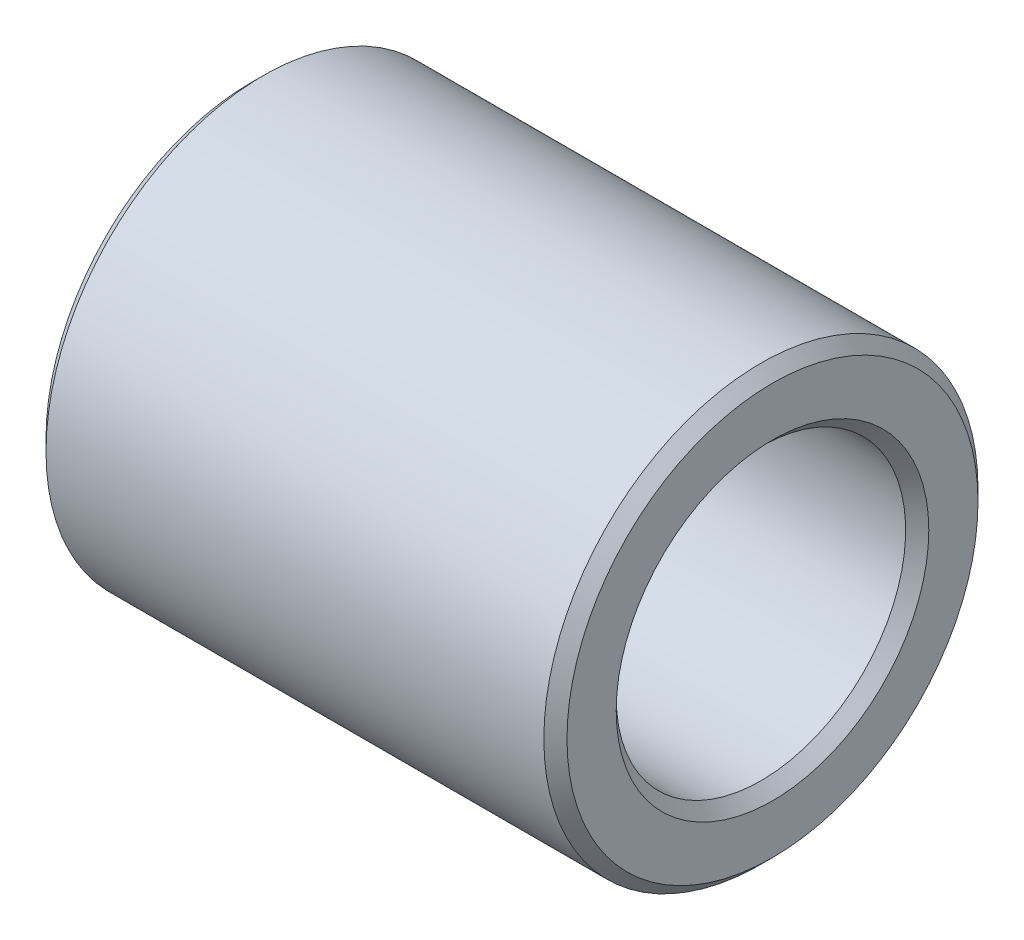
SolidWorks part; units mm, degrees
material "6061-T6 (SS)"
ref_plane "Front Plane" through (0, 0, 0) normal (0, 0, 1) x (1, 0, 0)
ref_plane "Top Plane" through (0, 0, 0) normal (0, 1, 0) x (1, 0, 0)
ref_plane "Right Plane" through (0, 0, 0) normal (1, 0, 0) x (0, 0, -1)
sketch "Sketch1" plane through (0, 0, 0) normal (0, 0, 1) x (1, 0, 0)
  line L0 (0, 6.35) -> (0, 0) construction
  line L1 (0, 6.35) -> (22.86, 6.35)
  line L5 (22.86, 9.525) -> (0, 9.525)
  line L6 (0, 9.525) -> (0, 6.35)
  line L7 (0, 0) -> (44.5396, 0) construction
  line L8 (22.86, 6.35) -> (22.86, 9.525)
  dimension "D1" = 12.7
  dimension "D2" = 19.05
  dimension "D5" = 22.86
revolve "Revolve1" add sketch "Sketch1" angle 360 about L7
chamfer "Chamfer1" distance 0.508 angle 45 4 edges at (0, 0, 6.35) (0, 0, 9.525) (22.86, 0, 6.35) (22.86, 0, 9.525)
equation "\"D1@Sketch1\"=1/2"
